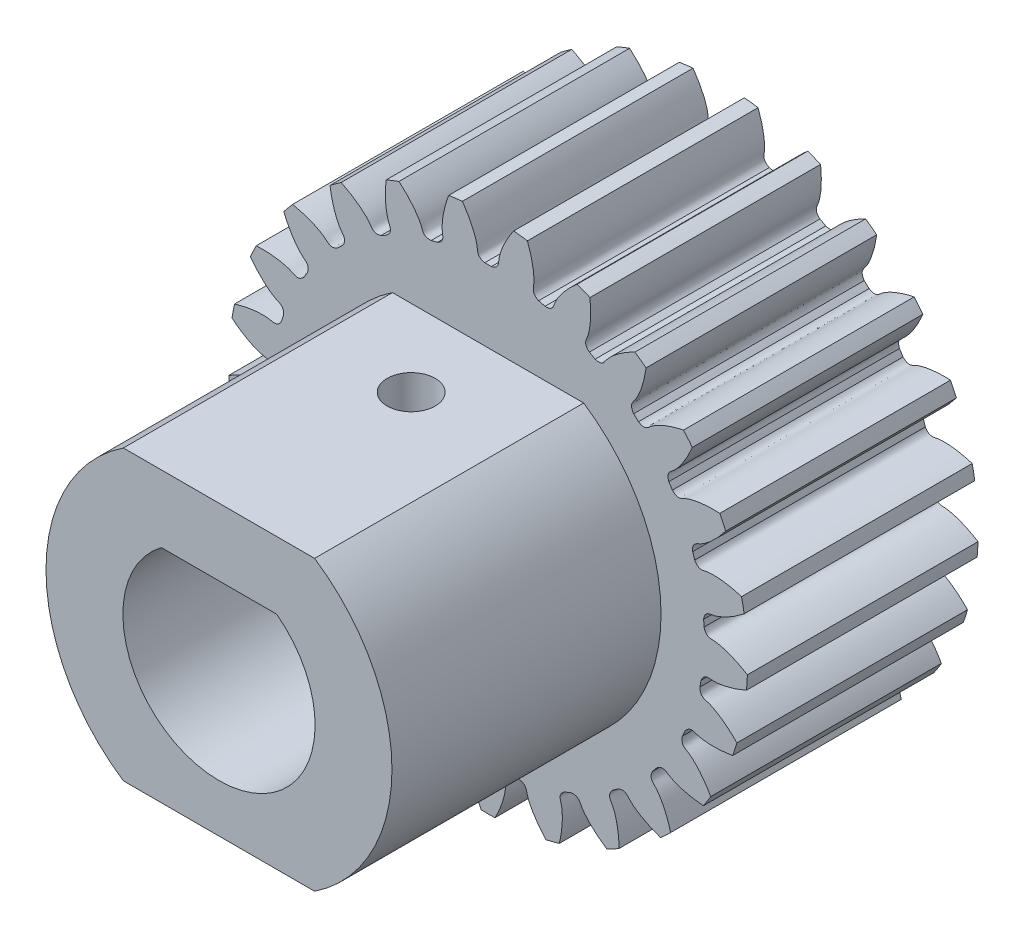
SolidWorks part; units mm, degrees
ref_plane "前视基准面" through (0, 0, 0) normal (0, 0, 1) x (1, 0, 0)
ref_plane "上视基准面" through (0, 0, 0) normal (0, 1, 0) x (1, 0, 0)
ref_plane "右视基准面" through (0, 0, 0) normal (1, 0, 0) x (0, 0, -1)
sketch "草图1" plane through (0, 0, 0) normal (0, 0, 1) x (1, 0, 0)
  circle A0 centre (0, 0) radius 13.5
extrude "凸台-拉伸1" add sketch "草图1" along normal blind 12
ref_axis "基准轴1" through (0, 0, 12) along (0, 0, -1)
sketch "草图2" plane through (0, 0, 0) normal (0, 0, 1) x (1, 0, 0)
  line L0 (0, 0) -> (0, 13.5) construction
  circle A0 centre (0, 0) radius 13.5 construction
  arc A1 (0.1721, 11.2487) -> (-0.1721, 11.2487) centre (0, 0) ccw
  arc A2 (3.2053, 15.3148) -> (-3.2053, 15.3148) centre (0, 0) ccw
  spline S0 degree 3 poles (0.1721, 11.2487) (0.5733, 11.3351) (0.5355, 11.5773) (0.5742, 11.8181) (0.5796, 11.8481) (0.5866, 11.8827) (0.5952, 11.9216) (0.6058, 11.965) (0.6184, 12.0127) (0.6332, 12.0647) (0.6505, 12.1208) (0.6704, 12.1811) (0.693, 12.2453) (0.7185, 12.3135) (0.7471, 12.3856) (0.779, 12.4614) (0.8143, 12.5408) (0.8532, 12.6238) (0.8958, 12.7102) (0.9423, 12.7998) (0.9928, 12.8927) (1.0475, 12.9886) (1.1065, 13.0875) (1.17, 13.1891) (1.238, 13.2934) (1.3108, 13.4002) (1.3884, 13.5093) (1.471, 13.6206) (1.5586, 13.734) (1.6515, 13.8493) (1.7496, 13.9663) (1.8532, 14.0848) (1.9623, 14.2047) (2.077, 14.3258) (2.1974, 14.448) (2.3235, 14.571) (2.4555, 14.6947) (2.5935, 14.8188) (2.7375, 14.9432) (2.94, 15.1113) (3.0975, 15.2341) (3.2053, 15.3148) knots 0 0 0 0 0.130741 0.135745 0.141658 0.148481 0.156214 0.164857 0.174409 0.184871 0.196243 0.208524 0.221715 0.235816 0.250827 0.266748 0.283578 0.301318 0.319968 0.339527 0.359996 0.381375 0.403664 0.426862 0.450971 0.475988 0.501916 0.528753 0.556501 0.585157 0.614724 0.6452 0.676587 0.708882 0.742088 0.776203 0.811228 0.847163 0.884008 0.921762 1 1 1 1
  spline S1 degree 3 poles (-0.1721, 11.2487) (-0.5733, 11.3351) (-0.5355, 11.5773) (-0.5742, 11.8181) (-0.5796, 11.8481) (-0.5866, 11.8827) (-0.5952, 11.9216) (-0.6058, 11.965) (-0.6184, 12.0127) (-0.6332, 12.0647) (-0.6505, 12.1208) (-0.6704, 12.1811) (-0.693, 12.2453) (-0.7185, 12.3135) (-0.7471, 12.3856) (-0.779, 12.4614) (-0.8143, 12.5408) (-0.8532, 12.6238) (-0.8958, 12.7102) (-0.9423, 12.7998) (-0.9928, 12.8927) (-1.0475, 12.9886) (-1.1065, 13.0875) (-1.17, 13.1891) (-1.238, 13.2934) (-1.3108, 13.4002) (-1.3884, 13.5093) (-1.471, 13.6206) (-1.5586, 13.734) (-1.6515, 13.8493) (-1.7496, 13.9663) (-1.8532, 14.0848) (-1.9623, 14.2047) (-2.077, 14.3258) (-2.1974, 14.448) (-2.3235, 14.571) (-2.4555, 14.6947) (-2.5935, 14.8188) (-2.7375, 14.9432) (-2.94, 15.1113) (-3.0975, 15.2341) (-3.2053, 15.3148) knots 0 0 0 0 0.130741 0.135745 0.141658 0.148481 0.156214 0.164857 0.174409 0.184871 0.196243 0.208524 0.221715 0.235816 0.250827 0.266748 0.283578 0.301318 0.319968 0.339527 0.359996 0.381375 0.403664 0.426862 0.450971 0.475988 0.501916 0.528753 0.556501 0.585157 0.614724 0.6452 0.676587 0.708882 0.742088 0.776203 0.811228 0.847163 0.884008 0.921762 1 1 1 1
extrude "切除-拉伸1" cut sketch "草图2" along normal through all
pattern_circular "阵列(圆周)1" count 25 every 14.4 about axis through (0, 0, 12) along (0, 0, -1) of "切除-拉伸1"
sketch "草图3" plane through (0, 0, 0) normal (0, 0, 1) x (1, 0, 0)
  circle A0 centre (0, 0) radius 12.5 construction
  dimension "Dn" = 25
sketch "草图4" plane through (0, 0, 12) normal (0, 0, 1) x (1, 0, 0)
  line L1 (3, 4) -> (-3, 4)
  arc A0 (-3, 4) -> (3, 4) centre (0, 0) ccw
  dimension "D1" = 4
  dimension "D2" = 10
extrude "切除-拉伸2" cut sketch "草图4" against normal through all both and the other way through all
sketch "草图5" plane through (0, 0, 12) normal (0, 0, 1) x (1, 0, 0)
  line L0 (3, 4) -> (-3, 4) construction
  line L1 (3, 4) -> (-3, 4)
  line L2 (-4.9749, 7.5) -> (4.9749, 7.5)
  line L3 (-4.9749, -7.5) -> (4.9749, -7.5)
  arc A0 (4.9749, -7.5) -> (4.9749, 7.5) centre (0, 0) ccw
  arc A1 (-3, 4) -> (3, 4) centre (0, 0) ccw construction
  arc A2 (-3, 4) -> (3, 4) centre (0, 0) ccw
  arc A3 (-4.9749, 7.5) -> (-4.9749, -7.5) centre (0, 0) ccw
  point P10 (0, 0)
  point P11 (-5.5673, -7.0714)
  dimension "D1" = 18
  dimension "D2" = 15
extrude "凸台-拉伸2" add sketch "草图5" along normal blind 14
sketch "草图6" plane through (0, 7.5, 0) normal (0, 1, 0) x (1, 0, 0)
  line L0 (4.9749, -26) -> (-4.9749, -26) construction
  circle A0 centre (0, -16) radius 1.25
  point P4 (0, 0)
  dimension "D1" = 10
  dimension "D2" = 2.5
extrude "切除-拉伸3" cut sketch "草图6" against normal through all both and the other way through all
sketch "草图7" plane through (0, 0, 0) normal (0, 0, -1) x (-1, 0, 0)
  line L0 (-3, 4) -> (3, 4) construction
  line L1 (-3, 4) -> (3, 4)
  arc A0 (-3, 4) -> (3, 4) centre (0, 0) ccw construction
  arc A1 (-3, 4) -> (3, 4) centre (0, 0) ccw
extrude "凸台-拉伸3" add sketch "草图7" against normal blind 5.8
sketch "草图8" plane through (0, 0, 0) normal (0, 0, -1) x (-1, 0, 0)
  circle A0 centre (0, 0) radius 2.2
  dimension "D1" = 4.4
extrude "切除-拉伸4" cut sketch "草图8" against normal through all both and the other way through all
sketch "草图9" plane through (0, 0, 0) normal (0, 0, -1) x (-1, 0, 0)
  circle A0 centre (0, 0) radius 4.5
  dimension "D1" = 9
extrude "切除-拉伸5" cut sketch "草图9" against normal blind 4
